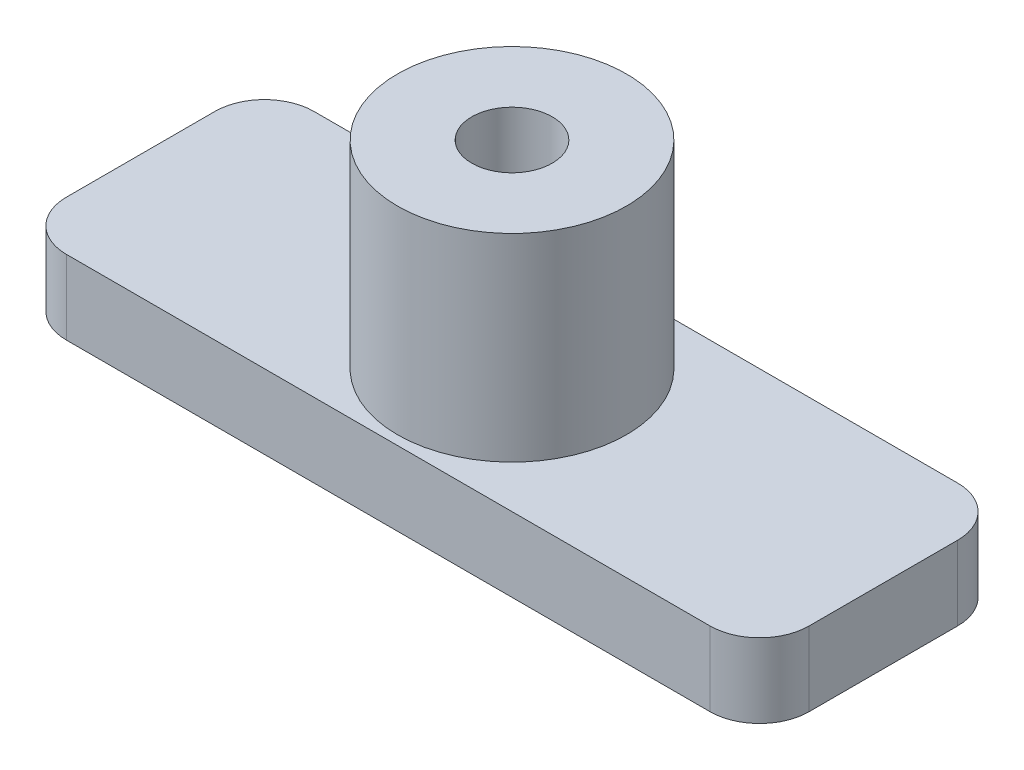
SolidWorks part; units mm, degrees
ref_plane "Front Plane" through (0, 0, 0) normal (0, 0, 1) x (1, 0, 0)
ref_plane "Top Plane" through (0, 0, 0) normal (0, 1, 0) x (1, 0, 0)
ref_plane "Right Plane" through (0, 0, 0) normal (1, 0, 0) x (0, 0, -1)
sketch "Sketch1" plane through (0, 0, 0) normal (0, 1, 0) x (1, 0, 0)
  line L1 (15, -5) -> (-15, -5)
  line L2 (15, -5) -> (15, 5)
  line L3 (15, 5) -> (-15, 5)
  line L4 (-15, -5) -> (-15, 5)
  line L5 (15, -5) -> (-15, 5) construction
  line L6 (15, 5) -> (-15, -5) construction
  point P0 (0, 0)
  dimension "D1" = 30
  dimension "D2" = 10
extrude "Boss-Extrude1" add sketch "Sketch1" along normal blind 3
sketch "Sketch2" plane through (0, 3, 0) normal (0, 1, 0) x (1, 0, 0)
  circle A0 centre (0, 0) radius 4.625
  circle A1 centre (0, 0) radius 1.625
  dimension "D1" = 3
  dimension "D2" = 3.25
extrude "Boss-Extrude2" add sketch "Sketch2" along normal blind 8
fillet "Fillet1" radius 2 4 edges at (15, 1.5, -5) (15, 1.5, 5) (-15, 1.5, -5) (-15, 1.5, 5)
